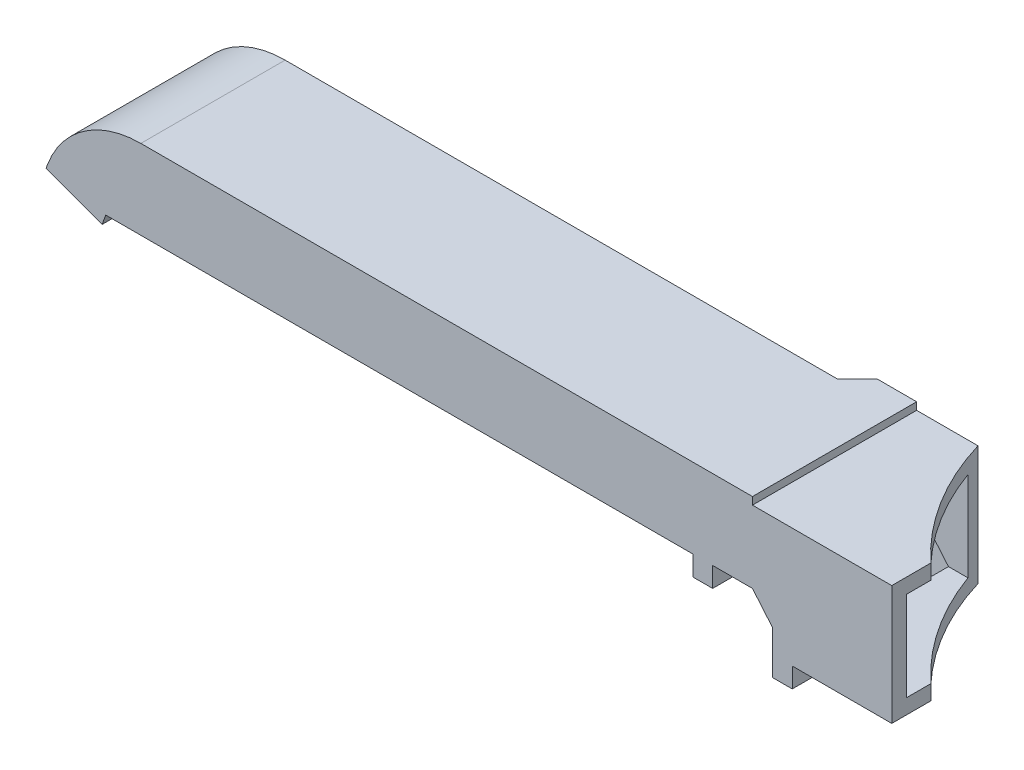
SolidWorks part; units mm, degrees
ref_plane "Plano frontal" through (0, 0, 0) normal (0, 0, 1) x (1, 0, 0)
ref_plane "Plano superior" through (0, 0, 0) normal (0, 1, 0) x (1, 0, 0)
ref_plane "Plano direito" through (0, 0, 0) normal (1, 0, 0) x (0, 0, -1)
sketch "Esboço1" plane through (0, 0, 0) normal (0, 0, 1) x (1, 0, 0)
  line L0 (9.5309, 0) -> (71, 0)
  line L1 (85, -0.75) -> (85, -12.75)
  line L2 (85, -12.75) -> (75, -12.75)
  line L3 (75, -12.75) -> (71, -8)
  line L4 (71, -8) -> (6.0021, -8)
  line L5 (71, 0) -> (71, -0.75)
  line L6 (0.134, -6.5798) -> (0, -6.9479)
  line L7 (0, -6.9479) -> (5.6382, -9)
  line L8 (5.6382, -9) -> (6.0021, -8)
  line L9 (71, -0.75) -> (85, -0.75)
  arc A0 (9.5309, 0) -> (0.134, -6.5798) centre (9.5309, -10) ccw
  point P15 (0, 0)
  dimension "D10" = 10
  dimension "D1" = 12
  dimension "D2" = 10
  dimension "D3" = 8
  dimension "D4" = 4
  dimension "D5" = 75
  dimension "D6" = 110
  dimension "D7" = 6
  dimension "D8" = 9
  dimension "D9" = 0.75
extrude "Ressalto-extrusão1" add sketch "Esboço1" along normal blind 16.5 contours L0 A0 L7 L8 L4 L3 L2 L1 L9 L5 region at (45.919, -4.611, 0)
sketch "Esboço2" plane through (0, 0, 16.5) normal (0, 0, 1) x (1, 0, 0)
  line L1 (-16.8833, 9.0488) -> (68, 9.0488)
  line L2 (-16.8833, 9.0488) -> (-16.8833, -13.9884)
  line L3 (-16.8833, -13.9884) -> (68, -13.9884)
  line L4 (68, 9.0488) -> (68, -13.9884)
  line L5 (85, -0.75) -> (85, -12.75) construction
  dimension "D1" = 17
extrude "Corte-extrusão1" cut sketch "Esboço2" against normal blind 14.5 from offset 14.5 offset against normal yes
chamfer "Chanfro1" distance 3 angle 45 1 edges at (68, -4, 2)
shell "Casca1" thickness 1.5 removed face at (2.8191, -7.9739, 9.25) removed face at (85, -6.75, 8.25)
sketch "Esboço4" plane through (0, -12.75, 0) normal (0, -1, 0) x (1, 0, 0)
  line L3 (77.1672, 0) -> (85, 0)
  line L4 (85, 0) -> (85, 12.567)
  arc A0 (85, 12.567) -> (77.1672, 0) centre (104, -8) ccw
  dimension "D3" = 28
  dimension "D1" = 19
  dimension "D2" = 8
extrude "Corte-extrusão2" cut sketch "Esboço4" against normal through all
sketch "Esboço5" plane through (0, 0, 16.5) normal (0, 0, 1) x (1, 0, 0)
  line L0 (71, -8) -> (6.0021, -8) construction
  line L1 (65, -8) -> (67, -8)
  line L2 (65, -8) -> (65, -10)
  line L3 (65, -10) -> (67, -10)
  line L4 (67, -8) -> (67, -10)
  line L5 (65, -8) -> (6.0021, -8) construction
  line L6 (75, -12.75) -> (71, -8) construction
  line L7 (75, -14.75) -> (73, -14.75)
  line L8 (75, -14.75) -> (75, -12.75)
  line L10 (73, -14.75) -> (73, -10.375)
  line L11 (85, -12.75) -> (75, -12.75) construction
  line L12 (73, -10.375) -> (75, -12.75)
  dimension "D1" = 2
  dimension "D2" = 2
  dimension "D3" = 2
  dimension "D4" = 2
extrude "Ressalto-extrusão2" add sketch "Esboço5" against normal blind 10
